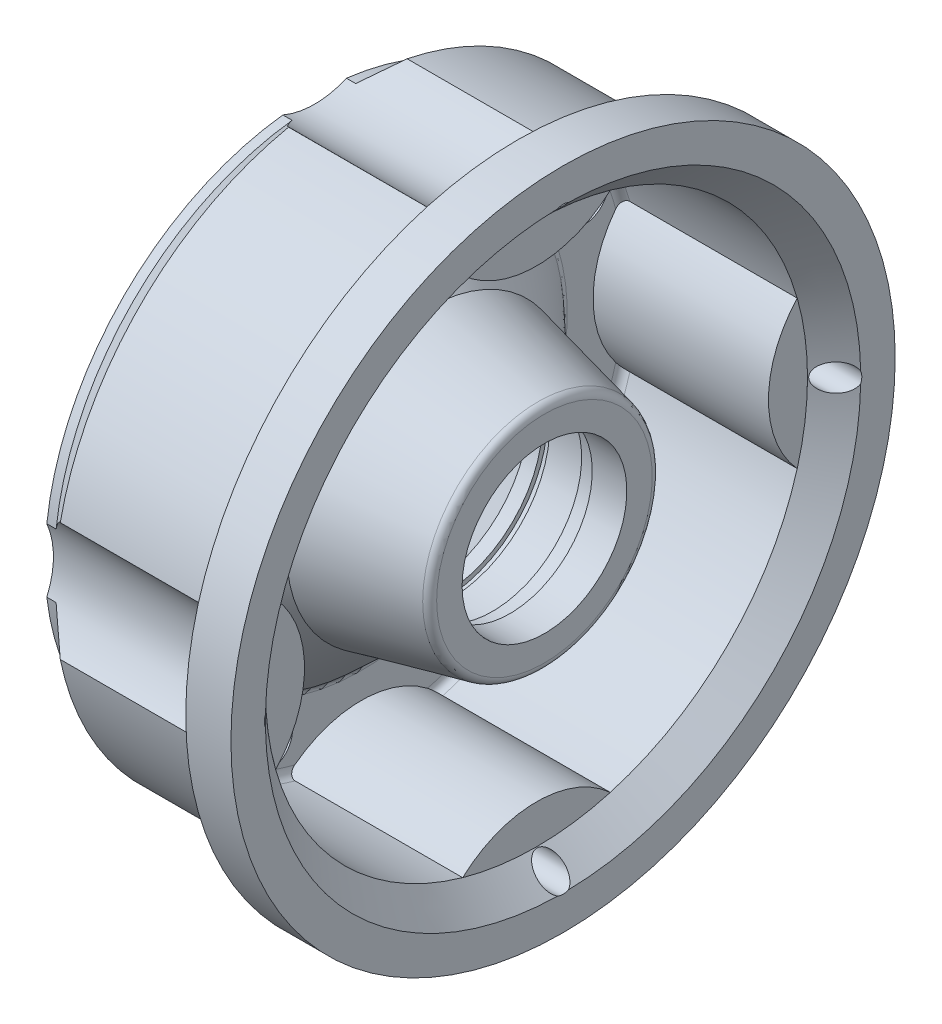
SolidWorks part; units mm, degrees
ref_plane "前视基准面" through (0, 0, 0) normal (0, 0, 1) x (1, 0, 0)
ref_plane "上视基准面" through (0, 0, 0) normal (0, 1, 0) x (1, 0, 0)
ref_plane "右视基准面" through (0, 0, 0) normal (1, 0, 0) x (0, 0, -1)
sketch "草图1" plane through (0, 0, 0) normal (0, 1, 0) x (1, 0, 0)
  line L0 (-80.4536, 0) -> (111.7711, 0) construction
  line L1 (0, -97.5) -> (0, -101.5)
  line L2 (0, -101.5) -> (3.5, -101.5)
  line L3 (3.5, -101.5) -> (12.5, -110.5)
  line L4 (12.5, -110.5) -> (73.5, -110.5)
  line L5 (76.5, -113.5) -> (76.5, -125)
  line L6 (76.5, -125) -> (93.5, -125)
  line L7 (93.5, -125) -> (93.5, -112.0292)
  line L8 (93.5, -112.0292) -> (83.4708, -102)
  line L9 (83.4708, -102) -> (20.5, -102)
  line L10 (17.5, -99) -> (17.5, -77.5967)
  line L11 (0, -97.5) -> (3.5, -97.5)
  line L12 (3.5, -97.5) -> (3.5, -80)
  line L13 (8.5, -80) -> (8.5, -72.5)
  line L14 (8.5, -72.5) -> (11.5, -72.5)
  line L15 (11.5, -72.5) -> (11.5, -66.8472)
  line L16 (11.5, -66.8472) -> (43, -37.5)
  line L17 (43, -37.5) -> (48.3, -37.5)
  line L18 (48.3, -37.5) -> (48.3, -39.25)
  line L19 (48.3, -39.25) -> (51, -39.25)
  line L20 (51, -39.25) -> (51, -37.5)
  line L21 (51, -37.5) -> (67, -37.5)
  line L22 (67, -37.5) -> (67, -33.5)
  line L23 (67, -33.5) -> (72.5, -33.5)
  line L24 (73.5, -32.5) -> (73.5, -31)
  line L25 (73.5, -31) -> (86.5, -31)
  line L26 (86.5, -31) -> (86.5, -40.5751)
  line L27 (84.1669, -43.5) -> (42.5, -53)
  line L28 (42.5, -53) -> (18.455, -75.4017)
  line L29 (8.5, -80) -> (3.5, -80)
  arc A0 (84.1669, -43.5) -> (86.5, -40.5751) centre (83.5, -40.5751) ccw
  arc A1 (73.5, -110.5) -> (76.5, -113.5) centre (73.5, -113.5) cw
  arc A2 (72.5, -33.5) -> (73.5, -32.5) centre (72.5, -32.5) ccw
  arc A3 (17.5, -99) -> (20.5, -102) centre (20.5, -99) ccw
  arc A4 (17.5, -77.5967) -> (18.455, -75.4017) centre (20.5, -77.5967) cw
  point P36 (27.25, -52.1736)
  point P39 (93.5, -118.5146)
  dimension "D28" = 3
  dimension "D29" = 3
  dimension "D31" = 1
  dimension "D34" = 3
  dimension "D35" = 3
  dimension "D1" = 250
  dimension "D2" = 221
  dimension "D3" = 203
  dimension "D4" = 195
  dimension "D5" = 9
  dimension "D6" = 3.5
  dimension "D7" = 3.5
  dimension "D8" = 93.5
  dimension "D9" = 86.5
  dimension "D10" = 160
  dimension "D11" = 145
  dimension "D12" = 3
  dimension "D13" = 5
  dimension "D14" = 75
  dimension "D15" = 78.5
  dimension "D16" = 75
  dimension "D17" = 2.7
  dimension "D18" = 8
  dimension "D19" = 16
  dimension "D20" = 13
  dimension "D21" = 67
  dimension "D22" = 62
  dimension "D23" = 106
  dimension "D24" = 17.5
  dimension "D25" = 25
  dimension "D26" = 12.9708
  dimension "D27" = 8.5
  dimension "D30" = 11
  dimension "D32" = 17
  dimension "D33" = 87
  dimension "D36" = 63.5
revolve "旋转1" add sketch "草图1" angle 360 about L0
sketch "草图2" plane through (76.5, 0, 0) normal (-1, 0, 0) x (0, 0, 1)
  line L0 (0, 131.6293) -> (0, 55.7786) construction
  arc A4 (-27.7782, 98.1446) -> (27.7782, 98.1446) centre (0, 128.3004) ccw
  circle A5 centre (0, 0) radius 102 construction
  arc A6 (27.7782, 98.1446) -> (-27.7782, 98.1446) centre (0, 0) ccw
  dimension "D3" = 82
extrude "凸台-拉伸1" add sketch "草图2" along normal up to next and the other way blind 7 contours A6 A4
pattern_circular "阵列(圆周)1" count 4 over 360 of "凸台-拉伸1"
sketch "草图3" plane through (76.5, 0, 0) normal (-1, 0, 0) x (0, 0, 1)
  arc A0 (-24.3998, 110.8463) -> (24.3998, 110.8463) centre (0, 128.3004) ccw
  circle A1 centre (0, 0) radius 113.5 construction
  arc A2 (24.3998, 110.8463) -> (-24.3998, 110.8463) centre (0, 0) ccw
  dimension "D1" = 60
extrude "切除-拉伸2" cut sketch "草图3" along normal through all
pattern_circular "阵列(圆周)2" count 4 over 360 about axis through (-80.4536, 0, 0) along (-1, 0, 0) of "切除-拉伸2"
sketch "草图4" plane through (76.5, 0, 0) normal (-1, 0, 0) x (0, 0, 1)
  line L0 (-14.0409, 0) -> (-118.2577, 0) construction
  circle A0 centre (0, 0) radius 107.5 construction
  dimension "D1" = 215
hole_wizard "M12 螺纹孔的螺纹孔钻头1" positions "3D草图2" profile "草图6" hole size "M12" standard "GB" end condition up to next
sketch3d "3D草图2"
  line L0 (76.5, 0, -14.0409) -> (76.5, 0, -118.2577) construction
  point P0 (76.5, 0, -107.3398)
sketch "草图6" plane through (76.5, 0, -107.3398) normal (0, 1, 0) x (0, 0, 1)
  line L0 (0, 0) -> (0, 17.001)
  line L1 (0, 17.001) -> (5.1, 17.001)
  line L2 (5.1, 17.001) -> (5.1, 0)
  line L5 (5.1, 0) -> (0, 0)
  line L11 (0, -6.35) -> (0, 107.95) construction
  dimension "通孔孔直径" = 10.2
  dimension "通孔孔深度" = 17.001
pattern_circular "阵列(圆周)3" count 4 over 360 about axis through (-80.4536, 0, 0) along (-1, 0, 0) of "M12 螺纹孔的螺纹孔钻头1"
sketch "草图7" plane through (17.5, 0, 0) normal (1, 0, 0) x (0, 0, -1)
  line L0 (0, 0) -> (34.8242, 84.073)
  line L1 (0, 0) -> (-34.8242, 84.073)
  line L2 (0, 0) -> (0, 128.3004) construction
  circle A0 centre (0, 0) radius 91 construction
  circle A1 centre (34.8242, 84.073) radius 9
  arc M10 (95.7947, 24.9875) -> (24.9875, 95.7947) centre (0, 0) ccw
  dimension "D1" = 182
  dimension "D2" = 45
  dimension "D4" = 18
  dimension "D3" = 22.5
extrude "切除-拉伸3" cut sketch "草图7" against normal blind 3.5 contours A1 M10 region at (17.5, 76.8012, -39.6831)
sketch "草图8" plane through (17.5, 0, 0) normal (1, 0, 0) x (0, 0, -1)
  circle A0 centre (34.8242, 84.073) radius 5.5
  dimension "D1" = 11
extrude "切除-拉伸4" cut sketch "草图8" against normal through all
pattern_circular "阵列(圆周)4" count 8 over 360 about axis through (-80.4536, 0, 0) along (-1, 0, 0) of "切除-拉伸4", "切除-拉伸3"
ref_plane "mateFace" through (3.5, 0, 0) normal (-1, 0, 0) x (0, 0, 1)
